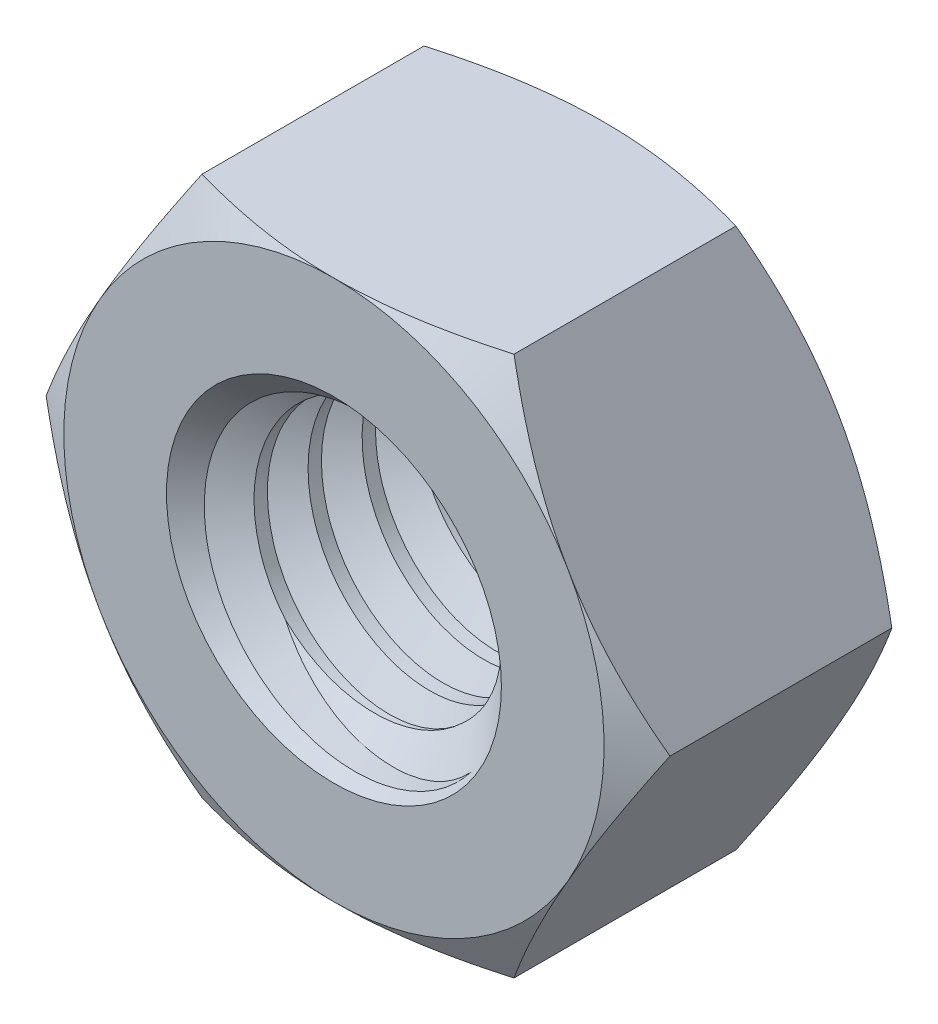
SolidWorks part; units mm, degrees
ref_plane "Front" through (0, 0, 0) normal (0, 0, 1) x (1, 0, 0)
ref_plane "Top" through (0, 0, 0) normal (0, 1, 0) x (1, 0, 0)
ref_plane "Right" through (0, 0, 0) normal (1, 0, 0) x (0, 0, -1)
sketch "Çizim1" plane through (0, 0, 0) normal (0, 0, 1) x (1, 0, 0)
  line L1 (5.7735, 0) -> (2.8868, 5)
  line L2 (2.8868, 5) -> (-2.8868, 5)
  line L3 (-2.8868, 5) -> (-5.7735, 0)
  line L4 (-5.7735, 0) -> (-2.8868, -5)
  line L5 (-2.8868, -5) -> (2.8868, -5)
  line L6 (2.8868, -5) -> (5.7735, 0)
  circle A0 centre (0, 0) radius 5 construction
  dimension "D1" = 10
extrude "Yükseklik-Ekstrüzyon1" add sketch "Çizim1" along normal blind 5
sketch "Çizim2" plane through (0, 0, 5) normal (0, 0, 1) x (1, 0, 0)
  circle A0 centre (0, 0) radius 5
extrude "Kes-Ekstrüzyon1" cut sketch "Çizim2" against normal blind 5 draft 60 flip side to cut
sketch "Çizim3" plane through (0, 0, 0) normal (0, 0, -1) x (-1, 0, 0)
  circle A0 centre (0, 0) radius 5
  dimension "D1" = 10
extrude "Kes-Ekstrüzyon2" cut sketch "Çizim3" against normal blind 5 draft 60 flip side to cut
sketch "Çizim4" plane through (0, 0, 0) normal (0, 0, -1) x (-1, 0, 0)
  circle A0 centre (0, 0) radius 2.35
  dimension "D1" = 4.7
extrude "Kes-Ekstrüzyon3" cut sketch "Çizim4" against normal blind 5
chamfer "Pah1" distance 0.75 angle 45 2 edges at (-2.35, 0, 0) (-2.35, 0, 5)
sketch "Çizim5" plane through (0, 0, 0) normal (0, 0, -1) x (-1, 0, 0)
  circle A0 centre (0, 0) radius 2.35
curve "Helis/Spiral1" pitch 1 height 6 radius 2.35 centre (0, 0, 0) axis (0, 0, 1) start towards (1, 0, 0)
ref_plane "Düzlem1" through (2.35, 0, 6) normal (0, 0.9977, 0.0676) x (1, 0, 0)
sketch "Çizim6" plane through (2.35, 0, 6) normal (0, 0.9977, 0.0676) x (1, 0, 0)
  line L1 (0.65, 0) -> (-0.1939, 0.4872)
  line L3 (-0.1939, -0.4872) -> (0.65, 0)
  line L4 (-0.1939, 0.4872) -> (-0.1939, -0.4872)
  line L5 (-0.325, 0.5629) -> (-0.325, 0) [skipped]
  circle A0 centre (0, 0) radius 0.325 construction
  dimension "D1" = 0.65
sweep "Kes-Süpür1" cut profiles "Çizim6" path "Helis/Spiral1" align with end faces yes
